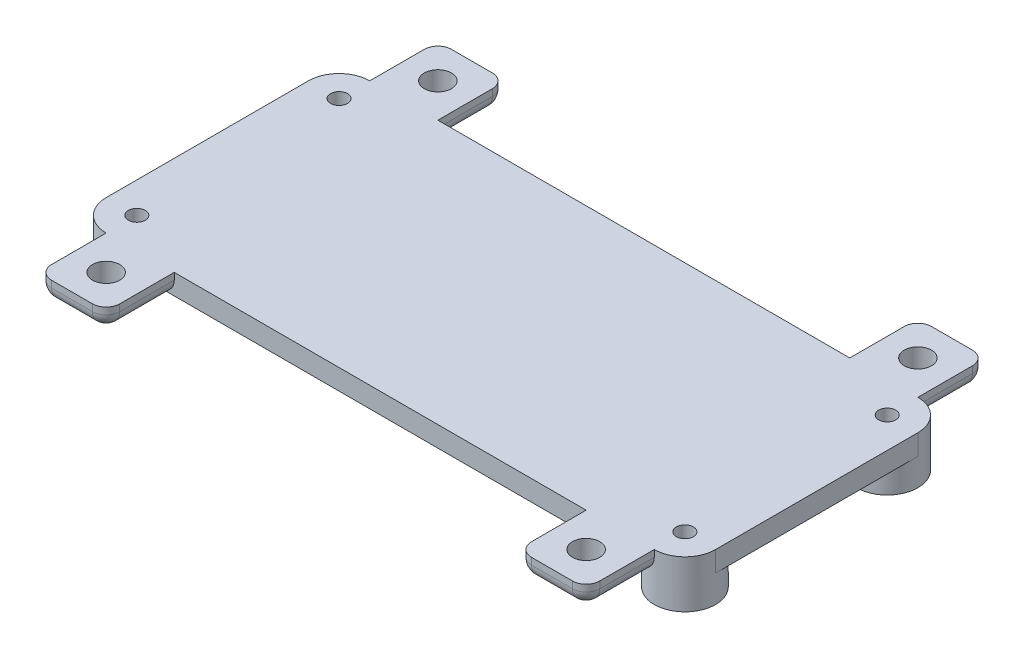
SolidWorks part; units mm, degrees
note: The reader was unsure of these and kept them because the rebuilt part matched: shared geometry of "Sketch1<3>", "Sketch3<2>".
ref_plane "Front Plane" through (0, 0, 0) normal (0, 0, 1) x (1, 0, 0)
ref_plane "Top Plane" through (0, 0, 0) normal (0, 1, 0) x (1, 0, 0)
ref_plane "Right Plane" through (0, 0, 0) normal (1, 0, 0) x (0, 0, -1)
sketch "Sketch1" plane through (0, 0, 0) normal (0, 1, 0) x (1, 0, 0)
  line L1 (0, 0) -> (-85.4, 0)
  line L2 (0, 0) -> (0, -35.22)
  line L3 (0, -35.22) -> (-85.4, -35.22)
  line L4 (-85.4, 0) -> (-85.4, -35.22)
  circle A0 centre (-2.395, -2.875) radius 1.25
  circle A1 centre (-82.845, -2.875) radius 1.25
  circle A2 centre (-82.845, -32.565) radius 1.25
  circle A3 centre (-2.395, -32.565) radius 1.25
  circle A4 centre (-82.845, -2.875) radius 4.5
  circle A5 centre (-2.395, -2.875) radius 4.5
  circle A6 centre (-2.395, -32.565) radius 4.5
  circle A7 centre (-82.845, -32.565) radius 4.5
  dimension "D3" = 2.5
  dimension "D8" = 9
  dimension "D1" = 35.22
  dimension "D2" = 85.4
  dimension "D4" = 2.395
  dimension "D5" = 2.875
  dimension "D6" = 2.655
  dimension "D7" = 2.555
extrude "Boss-Extrude1" add sketch "Sketch1" along normal blind 4 contours L4 A4 L1 A1 | L1 A4 L4 | L4 A7 L3 | L3 A7 L4 A2 | L2 A6 L3 A3 | L3 A6 L2 | L1 A5 L2 A0 | L2 A5 L1
sketch "Sketch2" plane through (0, 4, 0) normal (0, 1, 0) x (1, 0, 0)
  line L1 (-82.845, 1.625) -> (-2.395, 1.625)
  line L2 (-82.845, 1.625) -> (-82.845, -37.065)
  line L3 (-82.845, -37.065) -> (-2.395, -37.065)
  line L4 (-2.395, 1.625) -> (-2.395, -37.065)
  line L5 (2.105, -2.875) -> (-87.345, -2.875)
  line L6 (2.105, -2.875) -> (2.105, -32.565)
  line L7 (2.105, -32.565) -> (-87.345, -32.565)
  line L8 (-87.345, -2.875) -> (-87.345, -32.565)
  circle A0 centre (-82.845, -2.875) radius 4.5 construction
  circle A1 centre (-2.395, -32.565) radius 4.5 construction
  circle A2 centre (-2.395, -2.875) radius 4.5 construction
  circle A3 centre (-82.845, -32.565) radius 4.5 construction
  circle A4 centre (-82.845, -2.875) radius 4.5
  circle A5 centre (-82.845, -32.565) radius 4.5
  circle A6 centre (-2.395, -32.565) radius 4.5
  circle A7 centre (-2.395, -2.875) radius 4.5
  circle M1 centre (-82.845, -2.875) radius 4.5
  circle M2 centre (-82.845, -2.875) radius 1.25
extrude "Boss-Extrude2" add sketch "Sketch2" along normal blind 3 contours A7 L1 L5 M1 | L5 L2 M1 M2 | L5 L2 M2 M1 | L5 L2 M2 M1 | L5 L2 M1 M2 | A5 L2 L8 M1 | A7 L5 L2 A5 L7 A6 L4 M1 | L2 A5 L7 | L7 A5 L2 | L7 A5 L2 | L2 A5 L7 | A6 L7 A5 L3 | L7 A6 L4 | L4 A6 L7 | L4 A6 L7 | L7 A6 L4 | A7 L4 A6 L6 | L5 A7 L4 | L4 A7 L5 | L5 A7 L4 | L4 A7 L5
extrude "Cut-Extrude1" cut sketch "Sketch1<3>" along normal up to next (7 mm away) contours A1 | A0 | A3 | A2
sketch "Sketch1<3>" plane through (0, 0, 0) normal (0, 1, 0) x (1, 0, 0) same geometry as "Sketch1"
sketch "Sketch3" plane through (0, 0, -1.625) normal (0, 0, -1) x (-1, 0, 0)
  line L0 (82.845, 7) -> (2.395, 7) construction
  line L1 (82.845, 4) -> (72.845, 4)
  line L2 (82.845, 4) -> (82.845, 7)
  line L3 (82.845, 7) -> (72.845, 7)
  line L4 (72.845, 4) -> (72.845, 7)
  line L6 (2.395, 4) -> (12.395, 4)
  line L7 (2.395, 4) -> (2.395, 7)
  line L8 (2.395, 7) -> (12.395, 7)
  line L9 (12.395, 4) -> (12.395, 7)
  dimension "D1" = 10
extrude "Boss-Extrude3" add sketch "Sketch3" along normal blind 10
extrude "Boss-Extrude4" add sketch "Sketch3<2>" against normal blind 10 from surface at -38.69 starting at face at (-42.62, 5.5, 37.065)
sketch "Sketch3<2>" plane through (0, 0, -1.625) normal (0, 0, -1) x (-1, 0, 0) same geometry as "Sketch3"
fillet "Fillet1" radius 2 8 edges at (-72.845, 5.5, 47.065) (-82.845, 5.5, 47.065) (-12.395, 5.5, 47.065) (-2.395, 5.5, 47.065) (-2.395, 5.5, -11.625) (-12.395, 5.5, -11.625) (-72.845, 5.5, -11.625) (-82.845, 5.5, -11.625)
fillet "Fillet2" radius 2 20 edges at (-82.845, 4, 41.065) (-82.2592, 4, 46.4792) (-77.845, 4, 47.065) (-73.4308, 4, 46.4792) (-2.395, 4, 41.065) (-2.9808, 4, 46.4792) (-7.395, 4, 47.065) (-11.8092, 4, 46.4792) (-2.395, 4, -5.625) (-2.9808, 4, -11.0392) (-7.395, 4, -11.625) (-11.8092, 4, -11.0392) (-72.845, 4, -5.625) (-73.4308, 4, -11.0392) (-77.845, 4, -11.625) (-82.2592, 4, -11.0392) (-72.845, 4, 41.065) (-12.395, 4, 41.065) (-12.395, 4, -5.625) (-82.845, 4, -5.625)
sketch "Sketch4" plane through (0, 7, 0) normal (0, 1, 0) x (1, 0, 0)
  line L0 (-2.395, 9.625) -> (-2.395, 1.625) construction
  line L1 (-82.845, 9.625) -> (-82.845, 1.625) construction
  line L2 (-80.845, -47.065) -> (-74.845, -47.065) construction
  line L3 (-80.845, 11.625) -> (-74.845, 11.625) construction
  circle A0 centre (-77.845, 6.625) radius 2
  circle A1 centre (-7.395, 6.625) radius 2
  circle A2 centre (-7.395, -42.065) radius 2
  circle A3 centre (-77.845, -42.065) radius 2
  point P8 (0, 0)
  point P9 (0, 0)
  point P10 (0, 0)
  point P11 (0, 0)
  dimension "D5" = 4
  dimension "D1" = 5
  dimension "D2" = 5
  dimension "D3" = 5
  dimension "D4" = 5
extrude "Cut-Extrude2" cut sketch "Sketch4" against normal up to next
